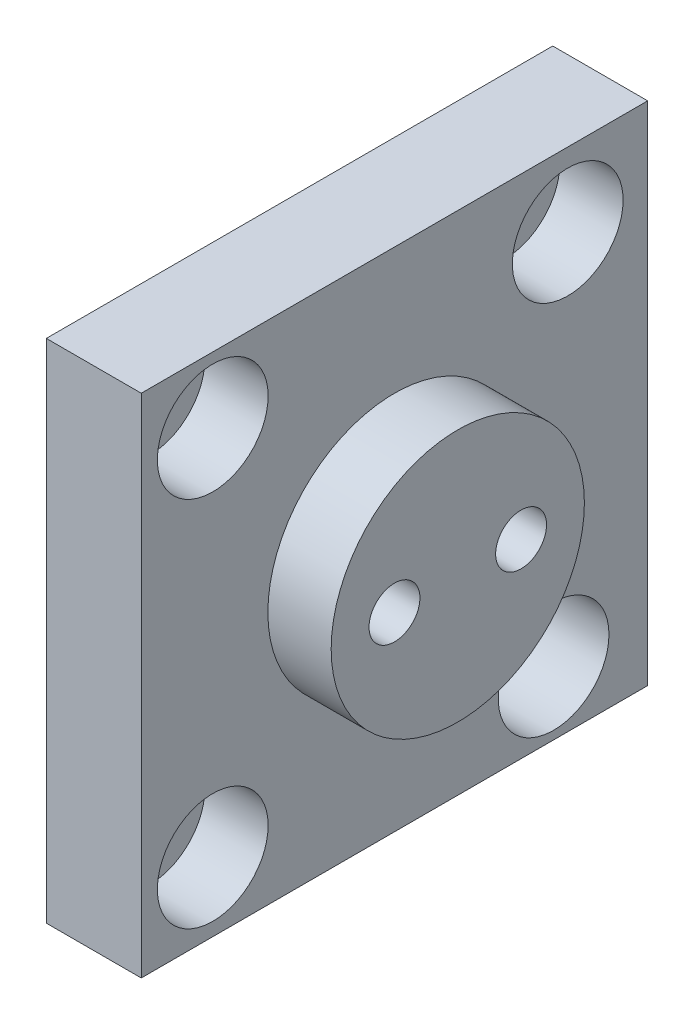
SolidWorks part; units mm, degrees
ref_plane "Front" through (0, 0, 0) normal (0, 0, 1) x (1, 0, 0)
ref_plane "Top" through (0, 0, 0) normal (0, 1, 0) x (1, 0, 0)
ref_plane "Right" through (0, 0, 0) normal (1, 0, 0) x (0, 0, -1)
sketch "Sketch1" plane through (0, 0, 0) normal (1, 0, 0) x (0, 0, -1)
  line L14 (-25.4, 25.4) -> (25.4, 25.4)
  line L15 (-25.4, 25.4) -> (-25.4, -25.4)
  line L16 (-25.4, -25.4) -> (25.4, -25.4)
  line L17 (25.4, 25.4) -> (25.4, -25.4)
  line L18 (-25.4, 25.4) -> (25.4, -25.4) construction
  line L19 (-25.4, -25.4) -> (25.4, 25.4) construction
  point P1 (0, 0)
  point P20 (-138.154, 23.5391)
  dimension "D1" = 50.8
  dimension "D2" = 50.8
extrude "Boss-Extrude1" add sketch "Sketch1" along normal blind 9.525
sketch "Sketch2" plane through (9.525, 0, 0) normal (1, 0, 0) x (0, 0, -1)
  circle A0 centre (0, 0) radius 12.7
  dimension "D1" = 25.4
extrude "Boss-Extrude2" add sketch "Sketch2" along normal blind 6.35
hole_wizard "1/4-20 Tapped Hole1" positions "Sketch3" profile "Sketch4" tap size "1/4-20" standard "ANSI Inch" end condition through all
sketch "Sketch3" plane through (15.875, 0, 0) normal (1, 0, 0) x (0, 0, -1)
  line L0 (0, 0) -> (0, -5.155) construction
  point P0 (-6.35, 0)
  point P2 (6.35, 0)
  point P7 (0, 0)
  dimension "D1" = 12.7
cosmetic thread "Hole Thread1" parameters "D2"=6.35
cosmetic thread "Hole Thread2" parameters "D2"=6.35
sketch "Sketch4" plane through (15.875, 0, 6.35) normal (0, 1, 0) x (0, 0, -1)
  line L0 (0, 0) -> (0, 15.875)
  line L1 (0, 15.875) -> (2.5527, 15.875)
  line L2 (2.5527, 15.875) -> (2.5527, 0)
  line L5 (2.5527, 0) -> (0, 0)
  line L11 (0, -6.35) -> (0, 107.95) construction
  dimension "Thru Tap Drill Dia." = 5.1054
  dimension "Thru Tap Drill Depth" = 15.875
hole_wizard "CBORE for 1/4 Socket Head Cap Screw1" positions "Sketch6" profile "Sketch7" counterbore size "1/4" standard "ANSI Inch" end condition through all
sketch "Sketch6" plane through (9.525, 0, 0) normal (1, 0, 0) x (0, 0, -1)
  point P0 (-18.2292, 18.7966)
  point P2 (17.378, 18.0164)
  point P4 (15.9594, -19.0094)
  point P6 (-18.2292, -18.5129)
sketch "Sketch7" plane through (9.525, 18.7966, 18.2292) normal (0, 1, 0) x (0, 0, -1)
  line L0 (0, 0) -> (0, 9.525)
  line L1 (0, 9.525) -> (3.3782, 9.525)
  line L3 (3.3782, 9.525) -> (3.3782, 6.35)
  line L4 (3.3782, 6.35) -> (5.5562, 6.35)
  line L5 (5.5562, 6.35) -> (5.5562, 0)
  line L7 (5.5562, 0) -> (0, 0)
  line L11 (0, -6.35) -> (0, 107.95) construction
  dimension "Thru Hole Dia." = 6.7564
  dimension "Thru Hole Depth" = 9.525
  dimension "C'Bore Dia." = 11.1125
  dimension "C'Bore Depth" = 6.35
